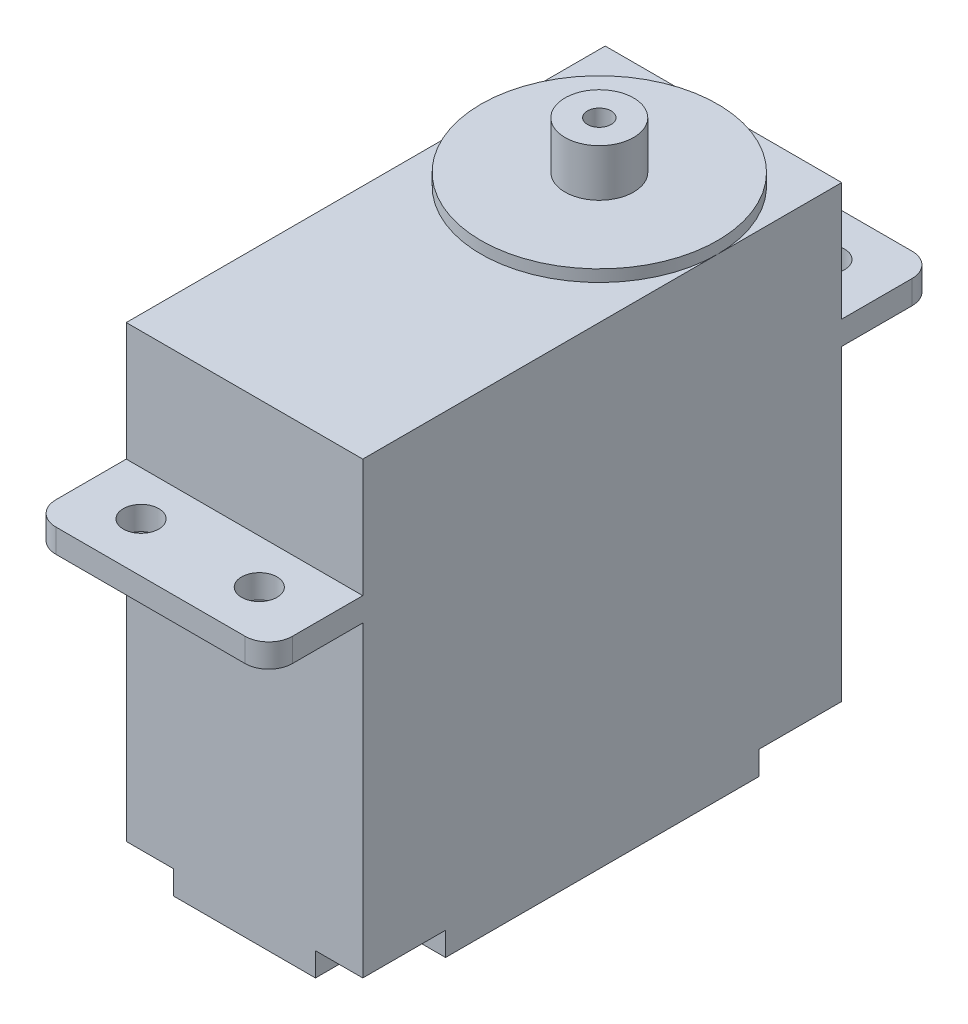
SolidWorks part; units mm, degrees
ref_plane "Front Plane" through (0, 0, 0) normal (0, 0, 1) x (1, 0, 0)
ref_plane "Top Plane" through (0, 0, 0) normal (0, 1, 0) x (1, 0, 0)
ref_plane "Right Plane" through (0, 0, 0) normal (1, 0, 0) x (0, 0, -1)
sketch "Sketch2" plane through (0, 77, 0) normal (0, 1, 0) x (1, 0, 0)
  line L1 (-49.2826, 255.8952) -> (-29.2826, 255.8952)
  line L2 (-49.2826, 255.8952) -> (-49.2826, 296.3952)
  line L3 (-49.2826, 296.3952) -> (-29.2826, 296.3952)
  line L4 (-29.2826, 255.8952) -> (-29.2826, 296.3952)
  dimension "D1" = 40.5
  dimension "D2" = 20
extrude "Boss-Extrude1" add sketch "Sketch2" along normal blind 28
sketch "Sketch3" plane through (0, 105, 0) normal (0, 1, 0) x (1, 0, 0)
  line L0 (-49.2826, 296.3952) -> (-49.2826, 255.8952) construction
  line L1 (-49.2826, 247.9452) -> (-29.2826, 247.9452)
  line L2 (-49.2826, 247.9452) -> (-49.2826, 304.3452)
  line L3 (-49.2826, 304.3452) -> (-29.2826, 304.3452)
  line L4 (-29.2826, 247.9452) -> (-29.2826, 304.3452)
  line L5 (-29.2826, 255.8952) -> (-29.2826, 296.3952) construction
  line L6 (-39.2826, 255.8952) -> (-39.2826, 296.3952) construction
  line L7 (-49.2826, 255.8952) -> (-29.2826, 255.8952) construction
  line L8 (-29.2826, 296.3952) -> (-49.2826, 296.3952) construction
  line L9 (-39.2826, 276.1452) -> (-34.2441, 276.1452) construction
  dimension "D1" = 0
  dimension "D2" = 0
  dimension "D3" = 56.4
  dimension "D4" = 28.2
extrude "Boss-Extrude2" add sketch "Sketch3" along normal blind 2
sketch "Sketch4" plane through (0, 107, 0) normal (0, 1, 0) x (1, 0, 0)
  line L4 (-49.2826, 296.3952) -> (-49.2826, 255.8952)
  line L5 (-29.2826, 296.3952) -> (-49.2826, 296.3952)
  line L6 (-29.2826, 255.8952) -> (-29.2826, 296.3952)
  line L7 (-49.2826, 255.8952) -> (-29.2826, 255.8952)
  line L8 (-49.2826, 296.3952) -> (-49.2826, 255.8952)
  line L9 (-29.2826, 296.3952) -> (-49.2826, 296.3952)
  line L10 (-29.2826, 255.8952) -> (-29.2826, 296.3952)
  line L11 (-49.2826, 255.8952) -> (-29.2826, 255.8952)
  dimension "D1" = 0
extrude "Boss-Extrude3" add sketch "Sketch4" along normal blind 10
sketch "Sketch5" plane through (0, 117, 0) normal (0, 1, 0) x (1, 0, 0)
  line L0 (-29.2826, 255.8952) -> (-29.2826, 296.3952) construction
  line L1 (-49.2826, 296.3952) -> (-49.2826, 255.8952) construction
  line L2 (-49.2826, 255.8952) -> (-29.2826, 255.8952) construction
  circle A0 centre (-39.2826, 285.8952) radius 10
  dimension "D1" = 30
extrude "Boss-Extrude4" add sketch "Sketch5" along normal blind 1
sketch "Sketch6" plane through (0, 118, 0) normal (0, 1, 0) x (1, 0, 0)
  circle A0 centre (-39.2826, 285.8952) radius 2.9
  circle A1 centre (-39.2826, 285.8952) radius 1
extrude "Boss-Extrude5" add sketch "Sketch6" along normal blind 4
sketch "Sketch7" plane through (0, 107, 0) normal (0, 1, 0) x (1, 0, 0)
  line L0 (-39.2826, 247.9452) -> (-39.2826, 304.3452) construction
  line L1 (-49.2826, 247.9452) -> (-29.2826, 247.9452) construction
  line L2 (-29.2826, 304.3452) -> (-49.2826, 304.3452) construction
  circle A0 centre (-44.2826, 252.1452) radius 1.5
  circle A1 centre (-34.2826, 252.1452) radius 1.5
  circle A2 centre (-34.2826, 300.1452) radius 1.5
  circle A3 centre (-44.2826, 300.1452) radius 1.5
extrude "Cut-Extrude1" cut sketch "Sketch7" against normal blind 2
fillet "Fillet1" radius 2 4 edges at (-29.2826, 106, -304.3452) (-49.2826, 106, -304.3452) (-49.2826, 106, -247.9452) (-29.2826, 106, -247.9452)
sketch "Sketch8" plane through (0, 77, 0) normal (0, -1, 0) x (1, 0, 0)
  line L0 (-39.2826, -255.8952) -> (-39.2826, -296.3952) construction
  line L1 (-29.2826, -255.8952) -> (-33.2826, -255.8952)
  line L2 (-29.2826, -255.8952) -> (-29.2826, -262.8952)
  line L3 (-29.2826, -262.8952) -> (-33.2826, -262.8952)
  line L4 (-33.2826, -255.8952) -> (-33.2826, -262.8952)
  line L5 (-49.2826, -255.8952) -> (-29.2826, -255.8952) construction
  line L6 (-29.2826, -296.3952) -> (-49.2826, -296.3952) construction
  line L7 (-29.2826, -276.1452) -> (-49.2826, -276.1452) construction
  line L8 (-29.2826, -255.8952) -> (-29.2826, -296.3952) construction
  line L9 (-49.2826, -296.3952) -> (-49.2826, -255.8952) construction
  line L10 (-33.2826, -296.3952) -> (-33.2826, -289.3952)
  line L11 (-29.2826, -289.3952) -> (-33.2826, -289.3952)
  line L12 (-29.2826, -296.3952) -> (-29.2826, -289.3952)
  line L13 (-29.2826, -296.3952) -> (-33.2826, -296.3952)
  line L14 (-49.2826, -296.3952) -> (-45.2826, -296.3952)
  line L15 (-49.2826, -296.3952) -> (-49.2826, -289.3952)
  line L16 (-49.2826, -289.3952) -> (-45.2826, -289.3952)
  line L17 (-45.2826, -296.3952) -> (-45.2826, -289.3952)
  line L18 (-45.2826, -255.8952) -> (-45.2826, -262.8952)
  line L19 (-49.2826, -262.8952) -> (-45.2826, -262.8952)
  line L20 (-49.2826, -255.8952) -> (-49.2826, -262.8952)
  line L21 (-49.2826, -255.8952) -> (-45.2826, -255.8952)
extrude "Cut-Extrude2" cut sketch "Sketch8" against normal blind 2
sketch "Sketch9" plane through (0, 0, -296.3952) normal (0, 0, -1) x (-1, 0, 0)
  line L0 (33.2826, 77) -> (45.2826, 77) construction
  line L1 (35.2826, 77) -> (43.2826, 77)
  line L2 (35.2826, 77) -> (35.2826, 80)
  line L3 (35.2826, 80) -> (43.2826, 80)
  line L4 (43.2826, 77) -> (43.2826, 80)
  line L5 (39.2826, 122) -> (39.2826, 77) construction
  line L6 (42.1826, 122) -> (36.3826, 122) construction
  dimension "D1" = 8
  dimension "D2" = 4
  dimension "D3" = 3
extrude "Boss-Extrude6" add sketch "Sketch9" along normal blind 5
ref_plane "Plane1" through (0, 124, 0) normal (0, 1, 0) x (1, 0, 0)
